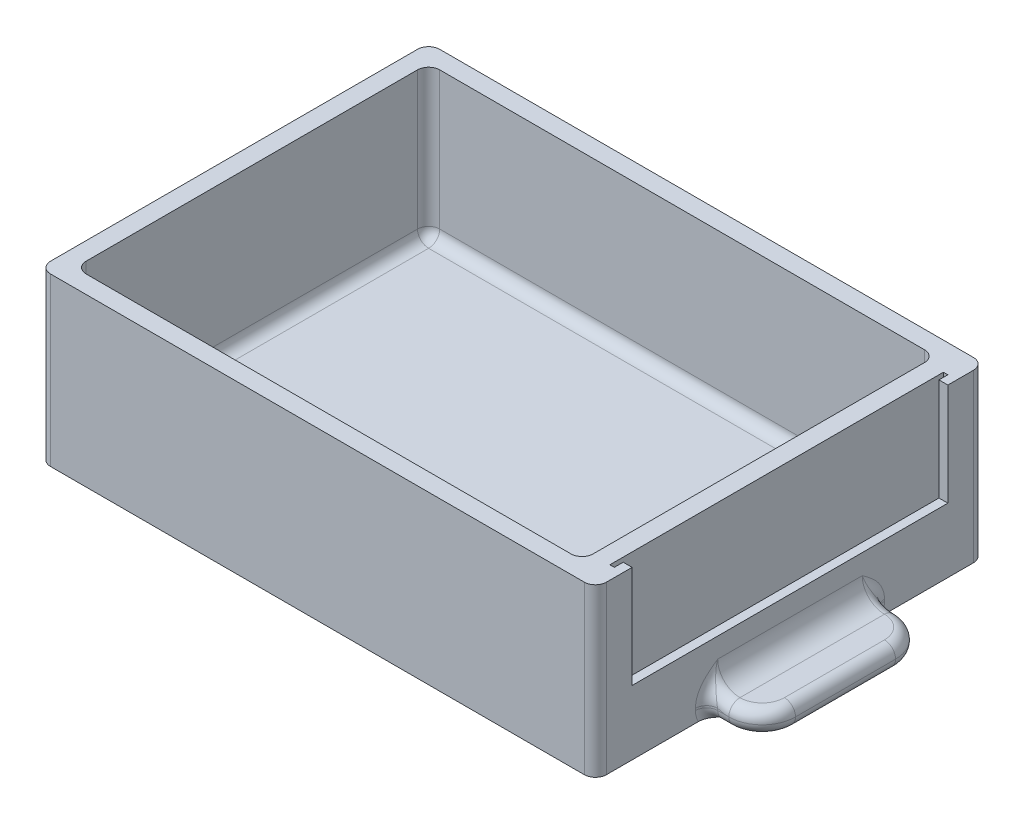
SolidWorks part; units mm, degrees
ref_plane "Спереди" through (0, 0, 0) normal (0, 0, 1) x (1, 0, 0)
ref_plane "Сверху" through (0, 0, 0) normal (0, 1, 0) x (1, 0, 0)
ref_plane "Справа" through (0, 0, 0) normal (1, 0, 0) x (0, 0, -1)
sketch "Эскиз1" plane through (0, 0, 0) normal (0, 1, 0) x (1, 0, 0)
  line L1 (-25, -17.5) -> (25, -17.5)
  line L2 (-25, -17.5) -> (-25, 17.5)
  line L3 (-25, 17.5) -> (25, 17.5)
  line L4 (25, -17.5) -> (25, 17.5)
  line L5 (-25, -17.5) -> (25, 17.5) construction
  line L6 (-25, 17.5) -> (25, -17.5) construction
  line L7 (-23.4, 15.9) -> (22.2, 15.9)
  line L8 (-23.4, 15.9) -> (-23.4, -15.9)
  line L9 (-23.4, -15.9) -> (22.2, -15.9)
  line L10 (22.2, 15.9) -> (22.2, -15.9)
  point P0 (0, 0)
  dimension "D1" = 50
  dimension "D2" = 35
  dimension "D3" = 1.6
  dimension "D4" = 1.6
  dimension "D5" = 1.6
  dimension "D6" = 2.8
extrude "Бобышка-Вытянуть1" add sketch "Эскиз1" along normal blind 15 contours L1 L4 L3 L2
extrude "Вырез-Вытянуть1" cut sketch "Эскиз1<3>" along normal through all from offset 1.6 contours L9 L10 L7 L8
sketch "Эскиз1<3>" plane through (0, 0, 0) normal (0, 1, 0) x (1, 0, 0) same geometry as "Эскиз1"
sketch "Эскиз2" plane through (25, 0, 0) normal (1, 0, 0) x (0, 0, -1)
  line L0 (-17.5, 15) -> (17.5, 15) construction
  line L1 (-15, 5) -> (15, 5)
  line L2 (-15, 5) -> (-15, 15)
  line L3 (-15, 15) -> (15, 15)
  line L4 (15, 5) -> (15, 15)
  line L5 (-15, 5) -> (15, 15) construction
  line L6 (-15, 15) -> (15, 5) construction
  line L8 (-14.2, 5.8) -> (14.2, 5.8)
  line L9 (-14.2, 5.8) -> (-14.2, 15)
  line L10 (-14.2, 15) -> (14.2, 15)
  line L11 (14.2, 5.8) -> (14.2, 15)
  line L12 (-14.2, 5.8) -> (14.2, 15) construction
  line L13 (-14.2, 15) -> (14.2, 5.8) construction
  point P0 (0, 10)
  point P7 (0, 10.4)
  dimension "D1" = 30
  dimension "D2" = 10
  dimension "D3" = 0.8
  dimension "D4" = 0.8
extrude "Вырез-Вытянуть2" cut sketch "Эскиз2" against normal blind 0.4 from offset 0.8 contours L2 L3 L4 L1 offset against normal yes
extrude "Вырез-Вытянуть3" cut sketch "Эскиз2<3>" against normal blind 0.8 contours L8 L11 L10 L9
sketch "Эскиз2<3>" plane through (25, 0, 0) normal (1, 0, 0) x (0, 0, -1) same geometry as "Эскиз2"
sketch "Эскиз3" plane through (0, 0, 0) normal (0, 0, 1) x (1, 0, 0)
  line L0 (25, 0) -> (25, 4)
  line L1 (25, 0) -> (30, 0)
  line L2 (30, 0) -> (30, 2)
  line L3 (30, 2) -> (27, 2)
  arc A0 (25, 4) -> (27, 2) centre (27, 4) ccw
  dimension "D3" = 2
  dimension "D1" = 5
  dimension "D2" = 2
extrude "Бобышка-Вытянуть2" add sketch "Эскиз3" along normal mid plane 15
fillet "Скругление1" radius 3 2 edges at (30, 1, -7.5) (30, 1, 7.5)
fillet "Скругление2" radius 1 10 edges at (25.5858, 2.5858, -7.5) (26, 0, -7.5) (29.1213, 0, -6.6213) (29.1213, 2, -6.6213) (26, 0, 7.5) (25.5858, 2.5858, 7.5) (29.1213, 2, 6.6213) (29.1213, 0, 6.6213) (30, 0, 0) (30, 2, 0) tangent propagation no
fillet "Скругление3" radius 1 6 edges at (25, 2.4562, -7.3808) (25, 0.2929, -7.2071) (25, 2.4562, 7.3808) (25, 0.2929, 7.2071) (25, 1.382, -7.5) (25, 1.382, 7.5)
fillet "Скругление4" radius 1 8 edges at (22.2, 8.3, 15.9) (22.2, 1.6, 0) (22.2, 8.3, -15.9) (-0.6, 1.6, -15.9) (-0.6, 1.6, 15.9) (-23.4, 1.6, 0) (-23.4, 8.3, 15.9) (-23.4, 8.3, -15.9)
fillet "Скругление5" radius 1 4 edges at (25, 7.5, -17.5) (-25, 7.5, -17.5) (-25, 7.5, 17.5) (25, 7.5, 17.5)
equation "\"D6@Эскиз1\"=1.6+0.4+0.8"
